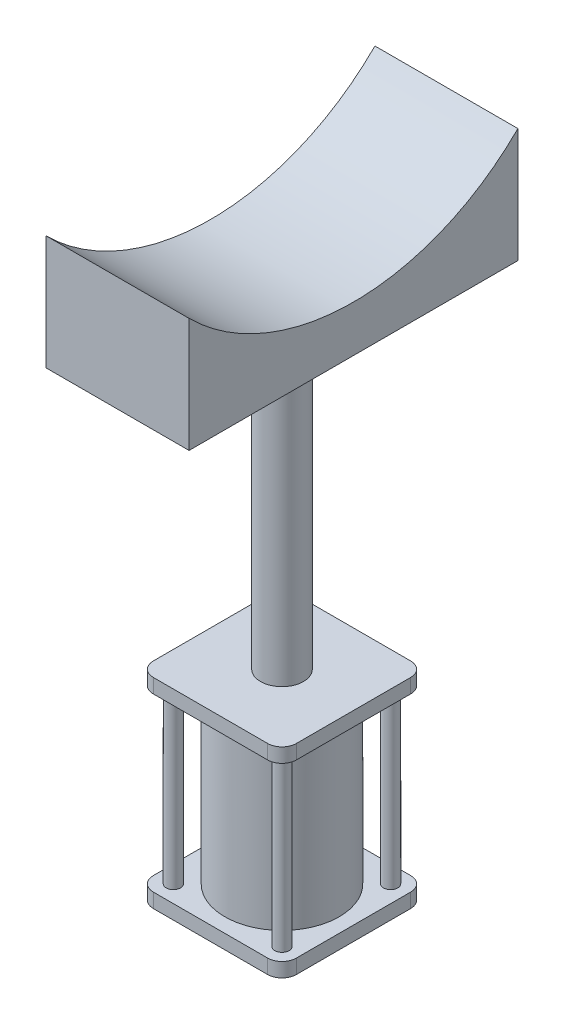
SolidWorks part; units mm, degrees
ref_plane "Front Plane" through (0, 0, 0) normal (0, 0, 1) x (1, 0, 0)
ref_plane "Top Plane" through (0, 0, 0) normal (0, 1, 0) x (1, 0, 0)
ref_plane "Right Plane" through (0, 0, 0) normal (1, 0, 0) x (0, 0, -1)
sketch "Sketch1" plane through (0, 0, 0) normal (0, 1, 0) x (1, 0, 0)
  line L1 (-50, -50) -> (50, -50)
  line L2 (-50, -50) -> (-50, 50)
  line L3 (-50, 50) -> (50, 50)
  line L4 (50, -50) -> (50, 50)
  line L5 (-50, -50) -> (50, 50) construction
  line L6 (-50, 50) -> (50, -50) construction
  point P0 (0, 0)
  dimension "D1" = 100
  dimension "D2" = 100
extrude "Boss-Extrude1" add sketch "Sketch1" along normal blind 10
sketch "Sketch2" plane through (0, 10, 0) normal (0, 1, 0) x (1, 0, 0)
  circle A0 centre (0, 0) radius 40
  dimension "D1" = 80
extrude "Boss-Extrude2" add sketch "Sketch2" along normal blind 120 separate body
sketch "Sketch3" plane through (0, 130, 0) normal (0, 1, 0) x (1, 0, 0)
  line L1 (-50, 50) -> (50, 50)
  line L2 (-50, 50) -> (-50, -50)
  line L3 (-50, -50) -> (50, -50)
  line L4 (50, 50) -> (50, -50)
extrude "Boss-Extrude3" add sketch "Sketch3" along normal blind 10 separate body
sketch "Sketch4" plane through (0, 140, 0) normal (0, 1, 0) x (1, 0, 0)
  circle A0 centre (0, 0) radius 15
  dimension "D1" = 30
extrude "Boss-Extrude4" add sketch "Sketch4" along normal blind 215 separate body
sketch "Sketch5" plane through (0, 10, 0) normal (0, 1, 0) x (1, 0, 0)
  line L0 (-50, 50) -> (-50, -50) construction
  line L1 (50, 50) -> (-50, 50) construction
  line L2 (0, 50) -> (0, 0) construction
  line L3 (0, 0) -> (50, 0) construction
  line L4 (50, -50) -> (50, 50) construction
  circle A0 centre (-38, 38) radius 5
  circle A1 centre (38, 38) radius 5
  circle A2 centre (38, -38) radius 5
  circle A3 centre (-38, -38) radius 5
  dimension "D1" = 10
  dimension "D2" = 12
  dimension "D3" = 12
extrude "Boss-Extrude5" add sketch "Sketch5" along normal up to surface (120 mm away) up to face at (0, 130, 0)
fillet "Fillet1" radius 10 8 edges at (50, 5, -50) (50, 5, 50) (-50, 5, 50) (-50, 5, -50) (-50, 135, -50) (50, 135, -50) (50, 135, 50) (-50, 135, 50)
sketch "Sketch6" plane through (0, 0, 0) normal (1, 0, 0) x (0, 0, -1)
  line L2 (-115, 435) -> (-115, 355)
  line L3 (-115, 355) -> (115, 355)
  line L4 (115, 435) -> (115, 355)
  line L5 (-15, 355) -> (-15, 140) construction
  line L6 (15, 140) -> (15, 355) construction
  line L7 (0, 355) -> (0, 2060) construction
  line L8 (-115, 395) -> (-90, 395) construction
  line L9 (-90, 395) -> (-90, 570) construction
  line L10 (15, 355) -> (-15, 355) construction
  arc A1 (-115, 435) -> (115, 435) centre (0, 550) ccw
  dimension "D1" = 80
  dimension "D2" = 80
  dimension "D3" = 100
  dimension "D4" = 100
  dimension "D5" = 0
extrude "Boss-Extrude6" add sketch "Sketch6" along normal blind 50 and the other way blind 50
